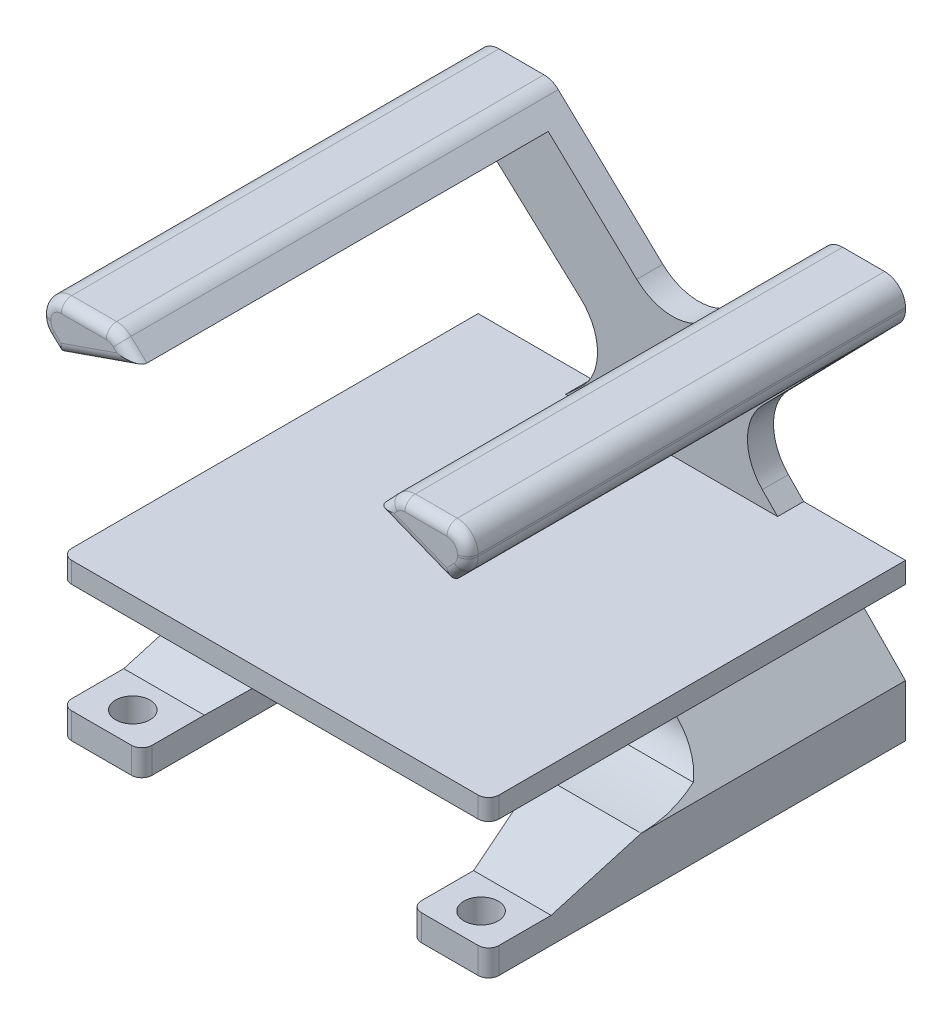
SolidWorks part; units mm, degrees
ref_plane "Front Plane" through (0, 0, 0) normal (0, 0, 1) x (1, 0, 0)
ref_plane "Top Plane" through (0, 0, 0) normal (0, 1, 0) x (1, 0, 0)
ref_plane "Right Plane" through (0, 0, 0) normal (1, 0, 0) x (0, 0, -1)
sketch "Sketch2" plane through (0, 0, 0) normal (0, 0, 1) x (1, 0, 0)
  line L0 (-21.3498, -15) -> (-12.6299, -7)
  line L1 (-21.3498, -20) -> (-16.3498, -20)
  line L2 (-21.3498, -20) -> (-21.3498, -15)
  line L3 (-21.3498, 20) -> (-16.3498, 20)
  line L4 (19.6502, -20) -> (19.6502, -15)
  line L5 (11.8368, -7) -> (19.6502, -7)
  line L6 (11.8368, -7) -> (19.6502, -15)
  line L7 (-21.3498, -5) -> (-10.4499, -5)
  line L8 (-21.3498, -5) -> (-21.3498, -7)
  line L9 (-21.3498, -7) -> (-12.6299, -7)
  line L10 (19.6502, -5) -> (19.6502, -7)
  line L11 (19.6502, 15) -> (19.6502, 20)
  line L12 (19.6502, -7) -> (19.6502, -5)
  line L13 (-5, 0) -> (-21.3498, 15)
  line L14 (-21.3498, 15) -> (-21.3498, 20)
  line L15 (-16.3498, 20) -> (0, 4.5233)
  line L16 (0, 4.5233) -> (14.6502, 20)
  line L17 (-2.18, -7) -> (1.9534, -7)
  line L18 (19.6502, 15) -> (5, 0)
  line L19 (5, 0) -> (9.8834, -5)
  line L20 (-21.3498, -7) -> (-21.3498, -5)
  line L21 (14.6502, -20) -> (1.9534, -7)
  line L22 (14.6502, 20) -> (19.6502, 20)
  line L23 (14.6502, -20) -> (19.6502, -20)
  line L24 (9.8834, -5) -> (19.6502, -5)
  line L26 (-10.4499, -5) -> (-5, 0)
  line L27 (-2.18, -7) -> (-16.3498, -20)
  point P0 (0, 0)
  point P6 (-0.8498, -6)
  dimension "D1" = 40
  dimension "D2" = 41
  dimension "D3" = 2
  dimension "D4" = 15
  dimension "D5" = 5
  dimension "D6" = 5
  dimension "D7" = 0
  dimension "D8" = 5
  dimension "D9" = 5
  dimension "D10" = 5
  dimension "D11" = 0
  dimension "D12" = 5
  dimension "D13" = 5
  dimension "D14" = 5
  dimension "D15" = 5
  dimension "D16" = 5
extrude "Boss-Extrude1" add sketch "Sketch2" along normal blind 40 contours L27 L17 L21 L23 L4 L6 L5 L10 L24 L19 L18 L11 L22 L16 L15 L3 L14 L13 L26 L7 L8 L9 L0 L2 L1
sketch "Sketch3" plane through (0, 0, 40) normal (0, 0, 1) x (1, 0, 0)
  line L0 (-21.3498, -5) -> (-10.4499, -5) construction
  line L1 (-19.5998, -5) -> (17.9002, -5)
  line L2 (-19.5998, -5) -> (-19.5998, 16)
  line L3 (-19.5998, 16) -> (17.9002, 16)
  line L4 (17.9002, -5) -> (17.9002, 16)
  line L5 (-21.3498, -5) -> (-21.3498, -7) construction
  line L6 (-21.3498, 15) -> (-21.3498, 20) construction
  line L7 (-21.3498, 18) -> (19.6502, 18)
  line L8 (-21.3498, 18) -> (-21.3498, 20)
  line L9 (-21.3498, 20) -> (19.6502, 20)
  line L10 (19.6502, 18) -> (19.6502, 20)
  dimension "D1" = 21
  dimension "D2" = 37.5
  dimension "D3" = 1.75
  dimension "D4" = 2
extrude "Cut-Extrude1" cut sketch "Sketch3" against normal blind 37.5
sketch "Sketch4" plane through (0, 18, 0) normal (0, 1, 0) x (1, 0, 0)
  line L1 (-21.3498, -2.5) -> (28.9336, -2.5)
  line L2 (-21.3498, -2.5) -> (-21.3498, 51.8334)
  line L3 (-21.3498, 51.8334) -> (28.9336, 51.8334)
  line L4 (28.9336, -2.5) -> (28.9336, 51.8334)
extrude "Cut-Extrude2" cut sketch "Sketch4" along normal blind 37.5
sketch "Sketch5" plane through (0, 0, 40) normal (0, 0, 1) x (1, 0, 0)
  line L0 (-21.3498, 15) -> (-19.5998, 13.3945)
  line L1 (-19.5998, 13.3945) -> (-12.1241, 16)
  line L2 (-12.1241, 16) -> (-14.237, 18)
  line L3 (-14.237, 18) -> (-21.3498, 18)
  line L4 (-21.3498, 18) -> (-21.3498, 15)
  line L5 (10.8638, 16) -> (12.757, 18)
  line L6 (12.757, 18) -> (19.6502, 18)
  line L7 (19.6502, 18) -> (19.6502, 15)
  line L8 (19.6502, 15) -> (17.9002, 13.2082)
  line L9 (17.9002, 13.2082) -> (10.8638, 16)
extrude "Boss-Extrude2" add sketch "Sketch5" along normal blind 2
sketch "Sketch6" plane through (19.6502, 0, 0) normal (1, 0, 0) x (0, 0, -1)
  line L0 (-40, -7) -> (0, -7) construction
  line L1 (-40, -15) -> (-10, -15)
  line L2 (-40, -15) -> (-40, -7)
  line L3 (-40, -7) -> (-10, -7)
  line L4 (-10, -15) -> (-10, -7)
  dimension "D1" = 30
extrude "Cut-Extrude3" cut sketch "Sketch6" against normal blind 100
chamfer "Chamfer1" distance 10 angle 30 2 edges at (-16.1248, -15, 10) (14.7085, -15, 10)
fillet "Fillet2" radius 20 4 edges at (-9.8318, -9.2265, 10) (-16.1248, -15, 20) (9.0696, -9.2265, 10) (14.7085, -15, 20)
fillet "Fillet3" radius 4 2 edges at (6.8951, -7, 10) (-7.4049, -7, 10)
fillet "Fillet4" radius 5 5 edges at (1.9534, -7, 10.9994) (-2.18, -7, 10.9994) (0, 4.5233, 1.25) (-5, 0, 1.25) (5, 0, 1.25)
sketch "Sketch7" plane through (19.6502, 0, 0) normal (1, 0, 0) x (0, 0, -1)
  line L0 (-40, -17.5) -> (-34, -17.5)
  line L1 (-40, -20) -> (-40, -15) construction
  line L2 (-34, -17.5) -> (-25.359, -15)
  line L3 (-25.359, -15) -> (-40, -15)
  line L4 (-40, -15) -> (-40, -17.5)
  dimension "D1" = 6
extrude "Cut-Extrude4" cut sketch "Sketch7" against normal blind 100
sketch "Sketch8" plane through (0, 0, 40) normal (0, 0, 1) x (1, 0, 0)
  line L0 (-13.6248, -17.5) -> (-16.3498, -20)
  line L1 (-13.6248, -17.5) -> (-16.3498, -20) construction
  line L2 (-3.614, -8.3157) -> (-16.3498, -20) construction
  line L3 (-16.3498, -20) -> (-13.6248, -20)
  line L4 (-13.6248, -20) -> (-13.6248, -17.5)
  line L5 (14.6502, -20) -> (12.2085, -17.5)
  line L6 (12.2085, -17.5) -> (12.2085, -20)
  line L7 (12.2085, -20) -> (14.6502, -20)
extrude "Boss-Extrude3" add sketch "Sketch8" against normal up to surface (40 mm away) up to face at (-0.5483, -2.3831, 0)
sketch "Sketch9" plane through (0, -17.5, 0) normal (0, 1, 0) x (1, 0, 0)
  line L0 (-21.3498, -40) -> (-13.6248, -40) construction
  line L1 (12.2085, -40) -> (19.6502, -40) construction
  circle A0 centre (-17.4873, -37) radius 1.65
  circle A1 centre (15.9294, -37) radius 1.65
  dimension "D1" = 3
  dimension "D2" = 3
extrude "Cut-Extrude5" cut sketch "Sketch9" against normal blind 100
sketch "Sketch10" plane through (0, 0, 0) normal (0, 0, -1) x (-1, 0, 0)
  line L0 (6.6248, -17.5) -> (13.6248, -17.5)
  line L1 (-12.2085, -20) -> (-5.2085, -20)
  line L2 (-12.2085, -20) -> (-12.2085, -17.5)
  line L3 (-12.2085, -17.5) -> (-5.2085, -17.5)
  line L4 (13.6248, -20) -> (13.6248, -17.5)
  line L6 (-5.2085, -17.5) -> (-5.2085, -20)
  line L8 (6.6248, -17.5) -> (6.6248, -20)
  line L9 (6.6248, -20) -> (13.6248, -20)
  dimension "D1" = 7
  dimension "D2" = 7
extrude "Boss-Extrude4" add sketch "Sketch10" against normal blind 5
sketch "Sketch11" plane through (0, -17.5, 0) normal (0, 1, 0) x (1, 0, 0)
  line L0 (5.2085, -5) -> (5.2085, 0) construction
  line L1 (-6.6248, -5) -> (-6.6248, 0) construction
  circle A0 centre (8.2085, -2.5) radius 1.65
  circle A1 centre (-9.6248, -2.5) radius 1.65
  dimension "D1" = 3
  dimension "D2" = 3
extrude "Cut-Extrude6" cut sketch "Sketch11" against normal blind 5
fillet "Fillet5" radius 1 2 edges at (-6.6248, -18.75, 5) (5.2085, -18.75, 5)
fillet "Fillet6" radius 1 2 edges at (-21.3498, -6, 40) (19.6502, -6, 40)
fillet "Fillet7" radius 2 6 edges at (19.6502, 18, 21) (-21.3498, 15, 21) (19.6502, 15, 21) (12.757, 18, 21) (-14.237, 18, 21) (-21.3498, 18, 21)
fillet "Fillet8" radius 1 16 edges at (-20.764, 17.4142, 42) (-17.1916, 18, 42) (-14.2935, 17.8581, 42) (-12.8913, 16.7262, 42) (-15.862, 14.6972, 42) (-20.1508, 13.9, 42) (-21.1806, 15.0744, 42) (-21.3498, 15.9396, 42) (19.5025, 15.0602, 42) (18.4906, 13.8127, 42) (14.382, 14.6041, 42) (11.5146, 16.6875, 42) (12.8271, 17.8371, 42) (15.634, 18, 42) (19.0644, 17.4142, 42) (19.6502, 15.9073, 42)
fillet "Fillet9" radius 1 4 edges at (-21.3498, -18.75, 40) (-13.6248, -18.75, 40) (19.6502, -18.75, 40) (12.2085, -18.75, 40)
